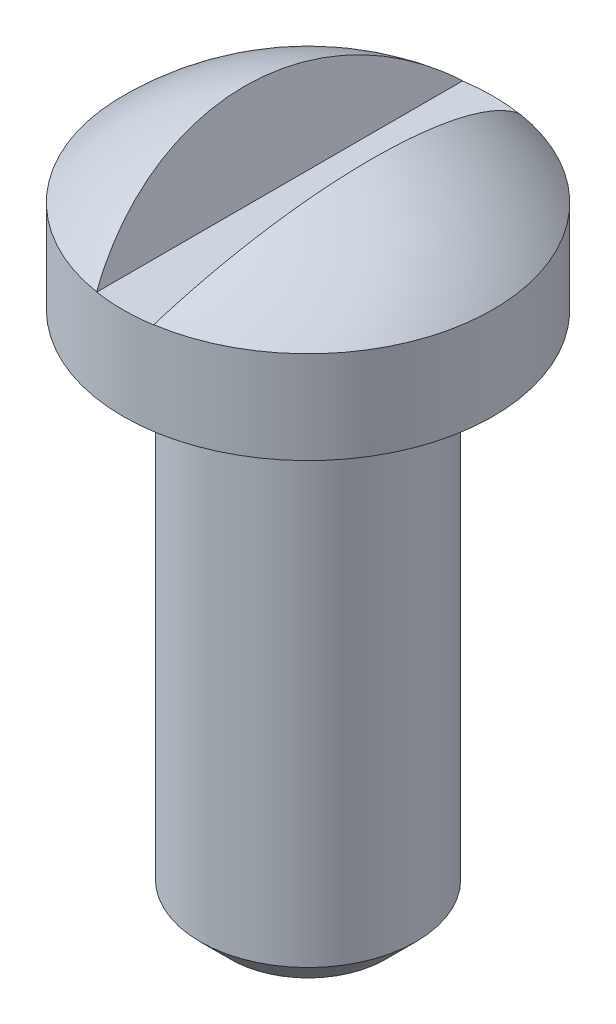
SolidWorks part; units mm, degrees
ref_plane "Front Plane" through (0, 0, 0) normal (0, 0, 1) x (1, 0, 0)
ref_plane "Top Plane" through (0, 0, 0) normal (0, 1, 0) x (1, 0, 0)
ref_plane "Right Plane" through (0, 0, 0) normal (1, 0, 0) x (0, 0, -1)
sketch "Sketch1" plane through (0, 0, 0) normal (0, 0, 1) x (1, 0, 0)
  line L0 (0, 93.461) -> (0, -88.5635)
sketch "Sketch2" plane through (0, 0, 0) normal (0, 0, 1) x (1, 0, 0)
  line L0 (-12.7, -40.1478) -> (0, -40.1478)
  line L1 (0, 93.461) -> (0, -88.5635) construction
  line L2 (-12.7, -40.1478) -> (-12.7, -42.6878)
  line L3 (-12.7, -42.6878) -> (-6.35, -42.6878)
  line L4 (-6.35, -42.6878) -> (-6.35, -85.8678)
  line L5 (-6.35, -85.8678) -> (0, -85.8678)
  line L6 (0, -25.7321) -> (0, -100.7901) construction
  dimension "D1" = 43.18
  dimension "D2" = 2.54
  dimension "D3" = 12.7
  dimension "D4" = 12.7
revolve "Revolve-Thin2" add sketch "Sketch2" angle 360 about L6 wall 2.54
chamfer "Chamfer1" distance 2.54 angle 45 1 edges at (0, -88.4078, 8.89)
dome "Dome1" faces to dome 1 distance 6.35 reverse direction no elliptical dome no face at (0, -37.6078, 15.24) parameters "D1"=6.35
sketch "Sketch11" plane through (0, 0, 0) normal (0, 0, 1) x (1, 0, 0)
sketch "Sketch15" plane through (0, 0, 0) normal (0, 0, 1) x (1, 0, 0)
  line L0 (0, -25.9822) -> (0, -61.2732) construction
  line L1 (2.3407, -37.6259) -> (-2.3407, -37.6259)
  line L2 (-2.3407, -37.6259) -> (-5.2125, -31.9003)
  line L3 (2.3407, -37.6259) -> (5.2125, -31.9003)
  arc A0 (15.24, -37.6078) -> (-15.24, -37.6078) centre (0, -52.7208) ccw construction
  point P3 (0, 0)
  point P11 (0, -37.6259)
sketch "Sketch16" plane through (0, 0, 0) normal (0, 0, 1) x (1, 0, 0)
extrude "Cut-Extrude5" cut sketch "Sketch15" against normal through all and the other way through all
